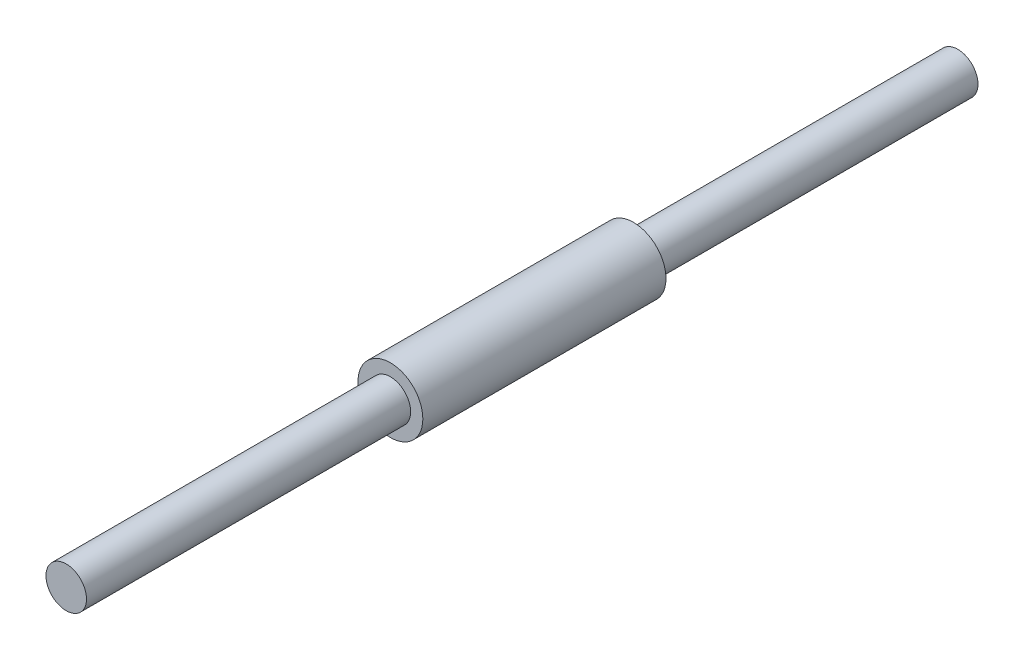
SolidWorks part; units mm, degrees
ref_plane "Front Plane" through (0, 0, 0) normal (0, 0, 1) x (1, 0, 0)
ref_plane "Top Plane" through (0, 0, 0) normal (0, 1, 0) x (1, 0, 0)
ref_plane "Right Plane" through (0, 0, 0) normal (1, 0, 0) x (0, 0, -1)
sketch "Sketch2" plane through (0, 0, 0) normal (0, 0, 1) x (1, 0, 0)
  circle A0 centre (0, 0) radius 3.175
  dimension "D1" = 6.35
extrude "Boss-Extrude1" add sketch "Sketch2" along normal blind 69.85 and the other way blind 69.85
sketch "Sketch3" plane through (0, 0, 0) normal (0, 0, 1) x (1, 0, 0)
  circle A0 centre (0, 0) radius 5.08
  dimension "D1" = 10.16
extrude "Boss-Extrude2" add sketch "Sketch3" along normal blind 19.05 and the other way blind 19.05
